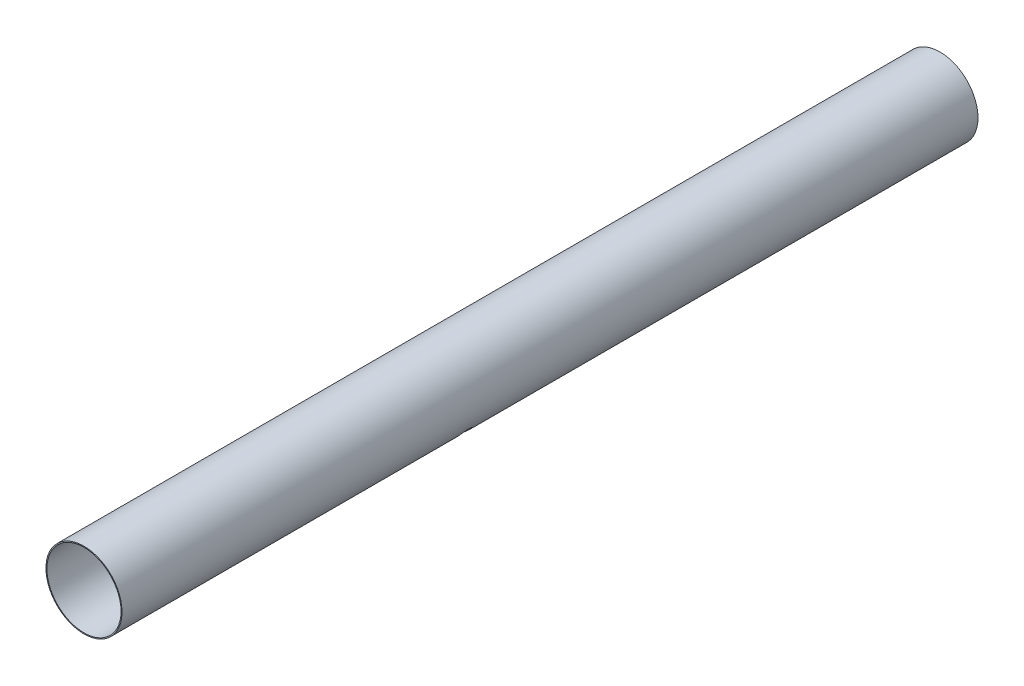
SolidWorks part; units mm, degrees
material "E-Glass Fiber"
ref_plane "Front" through (0, 0, 0) normal (0, 0, 1) x (1, 0, 0)
ref_plane "Top" through (0, 0, 0) normal (0, 1, 0) x (1, 0, 0)
ref_plane "Right" through (0, 0, 0) normal (1, 0, 0) x (0, 0, -1)
sketch "Sketch1" plane through (0, 0, 0) normal (0, 0, 1) x (1, 0, 0)
  circle A0 centre (0, 0) radius 78.2
  circle A1 centre (0, 0) radius 76.2
  dimension "D1" = 156.4
  dimension "D2" = 152.4
  dimension "D3" = 2
extrude "Boss-Extrude1" add sketch "Sketch1" along normal blind 1760
sketch "Sketch4" plane through (0, 0, 0) normal (0, 0, 1) x (1, 0, 0)
  line L0 (0, 0) -> (25.0476, -25.0476) construction
  line L1 (0, 0) -> (0, -24.8691) construction
  dimension "D1" = 45
ref_plane "Plane1" through (0, 0, 0) normal (0.7071, -0.7071, 0) x (0, 0, -1)
sketch "Sketch5" plane through (0, 0, 0) normal (0.7071, -0.7071, 0) x (0, 0, -1)
  line L0 (0, -78.2) -> (0, 78.2) construction
  circle A0 centre (-1034.89, 0) radius 15
  dimension "D1" = 30
  dimension "D2" = 1034.89
extrude "Cut-Extrude2" cut sketch "Sketch5" along normal through all
